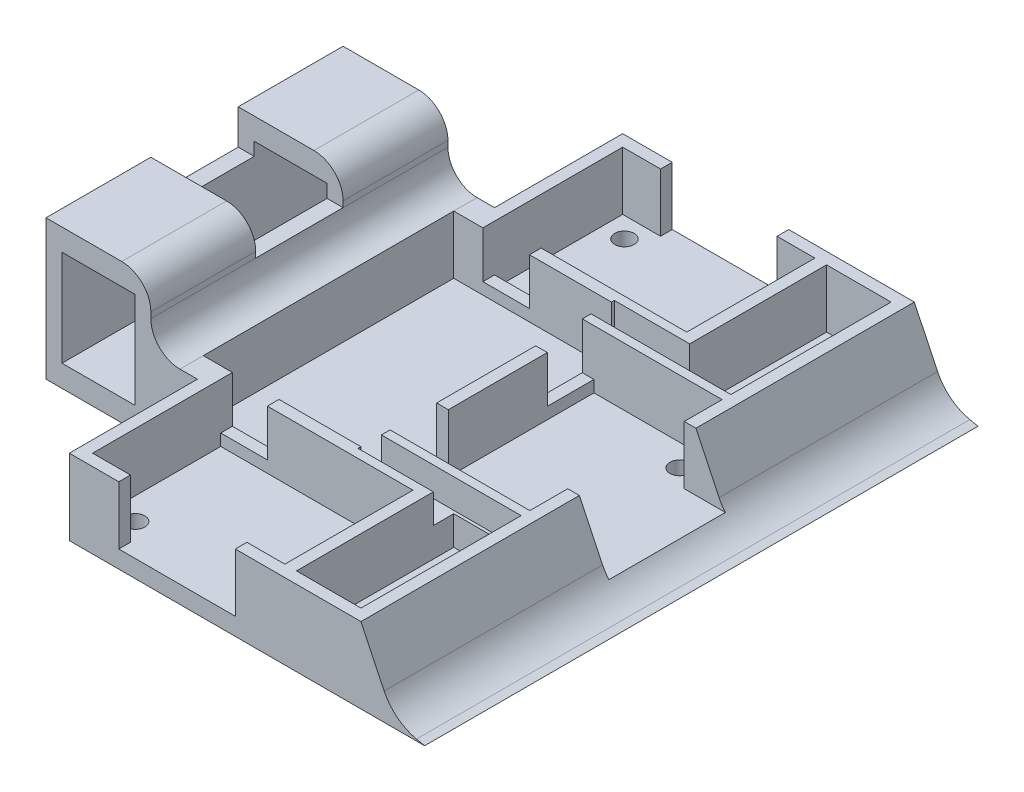
SolidWorks part; units mm, degrees
ref_plane "Front Plane" through (0, 0, 0) normal (0, 0, 1) x (1, 0, 0)
ref_plane "Top Plane" through (0, 0, 0) normal (0, 1, 0) x (1, 0, 0)
ref_plane "Right Plane" through (0, 0, 0) normal (1, 0, 0) x (0, 0, -1)
sketch "Sketch1" plane through (0, 0, 0) normal (0, 1, 0) x (1, 0, 0)
  line L1 (-47.5, -47.5) -> (47.5, -47.5)
  line L2 (-47.5, -47.5) -> (-47.5, 47.5)
  line L3 (-47.5, 47.5) -> (47.5, 47.5)
  line L4 (47.5, -47.5) -> (47.5, 47.5)
  line L5 (-47.5, -47.5) -> (47.5, 47.5) construction
  line L6 (-47.5, 47.5) -> (47.5, -47.5) construction
  point P0 (0, 0)
  dimension "D1" = 95
  dimension "D2" = 95
extrude "Boss-Extrude2" add sketch "Sketch1" along normal blind 13
sketch "Sketch2" plane through (-47.5, 0, 0) normal (-1, 0, 0) x (0, 0, 1)
  line L0 (-47.5, 13) -> (47.5, 13) construction
  line L1 (47.5, 0) -> (25.5, 0)
  line L2 (47.5, 0) -> (47.5, 13)
  line L3 (47.5, 13) -> (25.5, 13)
  line L4 (25.5, 0) -> (25.5, 13)
  dimension "D1" = 22
extrude "Cut-Extrude1" cut sketch "Sketch2" against normal blind 34
sketch "Sketch3" plane through (-47.5, 0, 0) normal (-1, 0, 0) x (0, 0, 1)
  line L0 (-47.5, 0) -> (25.5, 0) construction
  line L1 (-47.5, 13) -> (-25.5, 13)
  line L2 (-47.5, 13) -> (-47.5, 0)
  line L3 (-47.5, 0) -> (-25.5, 0)
  line L4 (-25.5, 13) -> (-25.5, 0)
  dimension "D1" = 22
extrude "Cut-Extrude2" cut sketch "Sketch3" against normal blind 34
sketch "Sketch5" plane through (0, 13, 0) normal (0, 1, 0) x (1, 0, 0)
  line L0 (-13.5, -25.5) -> (-47.5, -25.5) construction
  line L1 (-47.5, 25.5) -> (-21.5, 25.5)
  line L2 (-47.5, 25.5) -> (-47.5, -25.5)
  line L3 (-47.5, -25.5) -> (-21.5, -25.5)
  line L4 (-21.5, 25.5) -> (-21.5, -25.5)
  dimension "D1" = 26
extrude "Boss-Extrude3" add sketch "Sketch5" along normal blind 20
sketch "Sketch6" plane through (0, 0, 25.5) normal (0, 0, 1) x (1, 0, 0)
  line L0 (-13.5, 0) -> (-47.5, 0) construction
  line L1 (-36.5, 20) -> (-24.5, 20)
  line L2 (-36.5, 20) -> (-36.5, 4)
  line L3 (-36.5, 4) -> (-24.5, 4)
  line L4 (-24.5, 20) -> (-24.5, 4)
  line L5 (-47.5, 33) -> (-47.5, 0) construction
  line L6 (-13.5, 0) -> (-13.5, 13) construction
  dimension "D1" = 12
  dimension "D2" = 16
  dimension "D3" = 4
  dimension "D4" = 11
  dimension "D5" = 11
extrude "Cut-Extrude4" cut sketch "Sketch6" against normal blind 200
sketch "Sketch7" plane through (0, 0, 25.5) normal (0, 0, 1) x (1, 0, 0)
  line L0 (-21.5, 33) -> (-21.5, 13) construction
  line L1 (-47.5, 33) -> (-21.5, 33)
  line L2 (-47.5, 33) -> (-47.5, 24)
  line L3 (-47.5, 24) -> (-21.5, 24)
  line L4 (-21.5, 33) -> (-21.5, 24)
  dimension "D1" = 4
extrude "Cut-Extrude5" cut sketch "Sketch7" against normal blind 200
fillet "Fillet2" radius 5 2 edges at (-21.5, 24, 0)
sketch "Sketch8" plane through (0, 0, 25.5) normal (0, 0, 1) x (1, 0, 0)
  line L0 (-13.5, 0) -> (-47.5, 0) construction
  line L1 (-47.5, 24) -> (-39.5, 24)
  line L2 (-47.5, 24) -> (-47.5, 0)
  line L3 (-47.5, 0) -> (-39.5, 0)
  line L4 (-39.5, 24) -> (-39.5, 0)
  dimension "D1" = 3
extrude "Cut-Extrude6" cut sketch "Sketch8" against normal blind 200
sketch "Sketch9" plane through (0, 13, 0) normal (0, 1, 0) x (1, 0, 0)
  line L0 (-13.5, -47.5) -> (47.5, -47.5) construction
  line L1 (-11.5, -23.5) -> (21.5, -23.5)
  line L2 (-11.5, -23.5) -> (-11.5, -45.5)
  line L3 (-11.5, -45.5) -> (21.5, -45.5)
  line L4 (21.5, -23.5) -> (21.5, -45.5)
  dimension "D1" = 33
  dimension "D2" = 22
  dimension "D3" = 2
  dimension "D4" = 2
extrude "Cut-Extrude7" cut sketch "Sketch9" against normal blind 10
sketch "Sketch10" plane through (0, 0, 47.5) normal (0, 0, 1) x (1, 0, 0)
  line L0 (-13.5, 0) -> (47.5, 0) construction
  line L1 (-5, 13) -> (15, 13)
  line L2 (-5, 13) -> (-5, 3)
  line L3 (-5, 3) -> (15, 3)
  line L4 (15, 13) -> (15, 3)
  dimension "D1" = 20
  dimension "D2" = 10
  dimension "D3" = 3
  dimension "D4" = 6.5
extrude "Cut-Extrude10" cut sketch "Sketch10" against normal blind 10
sketch "Sketch13" plane through (0, 13, 0) normal (0, 1, 0) x (1, 0, 0)
  line L0 (47.5, 47.5) -> (-13.5, 47.5) construction
  line L1 (-11.5, 45.5) -> (21.5, 45.5)
  line L2 (-11.5, 45.5) -> (-11.5, 23.5)
  line L3 (-11.5, 23.5) -> (21.5, 23.5)
  line L4 (21.5, 45.5) -> (21.5, 23.5)
  line L5 (-13.5, 25.5) -> (-13.5, 47.5) construction
  dimension "D1" = 22
  dimension "D2" = 33
  dimension "D3" = 2
  dimension "D4" = 2
extrude "Cut-Extrude11" cut sketch "Sketch13" against normal blind 10
sketch "Sketch14" plane through (0, 0, -47.5) normal (0, 0, -1) x (-1, 0, 0)
  line L0 (-47.5, 13) -> (13.5, 13) construction
  line L1 (-15, 13) -> (5, 13)
  line L2 (-15, 13) -> (-15, 3)
  line L3 (-15, 3) -> (5, 3)
  line L4 (5, 13) -> (5, 3)
  dimension "D1" = 20
  dimension "D2" = 10
  dimension "D3" = 8.5
extrude "Cut-Extrude12" cut sketch "Sketch14" against normal blind 10
sketch "Sketch18" plane through (47.5, 0, 0) normal (1, 0, 0) x (0, 0, -1)
  line L0 (-47.5, 13) -> (47.5, 13) construction
  line L1 (10, 13) -> (-10, 13)
  line L2 (10, 13) -> (10, 3)
  line L3 (10, 3) -> (-10, 3)
  line L4 (-10, 13) -> (-10, 3)
  dimension "D1" = 10
  dimension "D2" = 20
  dimension "D3" = 13.5
  dimension "D4" = 13.5
extrude "Cut-Extrude16" cut sketch "Sketch18" against normal blind 50
sketch "Sketch19" plane through (0, 0, 47.5) normal (0, 0, 1) x (1, 0, 0)
  line L0 (47.5, 0) -> (42.2527, 1.1202)
  line L1 (42.2527, 1.1202) -> (36.5702, 13)
  line L2 (15, 13) -> (47.5, 13) construction
  line L4 (36.5702, 13) -> (47.5, 13)
  line L7 (47.5, 13) -> (47.5, 0)
extrude "Cut-Extrude17" cut sketch "Sketch19" against normal blind 100000
sketch "Sketch20" plane through (0, 13, 0) normal (0, 1, 0) x (1, 0, 0)
  line L1 (34.5702, -16.5) -> (12.5702, -16.5)
  line L2 (34.5702, -16.5) -> (34.5702, 16.5)
  line L3 (34.5702, 16.5) -> (12.5702, 16.5)
  line L4 (12.5702, -16.5) -> (12.5702, 16.5)
  line L5 (36.5702, -10) -> (36.5702, -47.5) construction
  dimension "D1" = 22
  dimension "D2" = 33
  dimension "D3" = 6.5
  dimension "D4" = 2
extrude "Cut-Extrude18" cut sketch "Sketch20" against normal blind 10
sketch "Sketch21" plane through (0, 13, 0) normal (0, 1, 0) x (1, 0, 0)
  line L0 (-16.5, 25.5) -> (-16.5, -25.5) construction
  line L1 (-16.5, -21.5) -> (10.5702, -21.5)
  line L2 (-16.5, -21.5) -> (-16.5, 21.5)
  line L3 (-16.5, 21.5) -> (10.5702, 21.5)
  line L4 (10.5702, -21.5) -> (10.5702, 21.5)
  dimension "D1" = 2
  dimension "D2" = 2
  dimension "D3" = 2
extrude "Cut-Extrude19" cut sketch "Sketch21" against normal blind 10
sketch "Sketch22" plane through (0, 3, 0) normal (0, 1, 0) x (1, 0, 0)
  line L1 (12.5702, -10) -> (10.5702, -10)
  line L2 (12.5702, -10) -> (12.5702, 10)
  line L3 (12.5702, 10) -> (10.5702, 10)
  line L4 (10.5702, -10) -> (10.5702, 10)
extrude "Boss-Extrude4" add sketch "Sketch22" along normal blind 10
sketch "Sketch23" plane through (0, 0, 25.5) normal (0, 0, 1) x (1, 0, 0)
  line L0 (-24.5, 20) -> (-36.5, 20) construction
  line L1 (-36.75, 20.25) -> (-24.25, 20.25)
  line L2 (-36.75, 20.25) -> (-36.75, 3.75)
  line L3 (-36.75, 3.75) -> (-24.25, 3.75)
  line L4 (-24.25, 20.25) -> (-24.25, 3.75)
  line L5 (-24.5, 4) -> (-24.5, 20) construction
  dimension "D1" = 12.5
  dimension "D2" = 16.5
  dimension "D3" = 0.25
  dimension "D4" = 0.25
extrude "Cut-Extrude20" cut sketch "Sketch23" against normal blind 200
sketch "Sketch24" plane through (0, 13, 0) normal (0, 1, 0) x (1, 0, 0)
  line L0 (-16.5, -21.5) -> (10.5702, -21.5) construction
  line L1 (-11.5, -23.5) -> (-3.5, -23.5)
  line L2 (-11.5, -23.5) -> (-11.5, -21.5)
  line L3 (-11.5, -21.5) -> (-3.5, -21.5)
  line L4 (-3.5, -23.5) -> (-3.5, -21.5)
  dimension "D1" = 8
extrude "Cut-Extrude21" cut sketch "Sketch24" against normal blind 8
sketch "Sketch25" plane through (0, 13, 0) normal (0, 1, 0) x (1, 0, 0)
  line L0 (10.5702, 21.5) -> (-16.5, 21.5) construction
  line L1 (-11.5, 23.5) -> (-3.5, 23.5)
  line L2 (-11.5, 23.5) -> (-11.5, 21.5)
  line L3 (-11.5, 21.5) -> (-3.5, 21.5)
  line L4 (-3.5, 23.5) -> (-3.5, 21.5)
  dimension "D1" = 8
extrude "Cut-Extrude22" cut sketch "Sketch25" against normal blind 8
sketch "Sketch26" plane through (0, 13, 0) normal (0, 1, 0) x (1, 0, 0)
  line L0 (10.5702, -21.5) -> (10.5702, 21.5) construction
  line L1 (12.5702, -16.5) -> (10.5702, -16.5)
  line L2 (12.5702, -16.5) -> (12.5702, -8.5)
  line L3 (12.5702, -8.5) -> (10.5702, -8.5)
  line L4 (10.5702, -16.5) -> (10.5702, -8.5)
  dimension "D1" = 8
extrude "Cut-Extrude24" cut sketch "Sketch26" against normal blind 8
sketch "Sketch27" plane through (0, 13, 0) normal (0, 1, 0) x (1, 0, 0)
  line L0 (10.5702, -8.5) -> (10.5702, 21.5) construction
  line L1 (12.5702, 16.5) -> (10.5702, 16.5)
  line L2 (12.5702, 16.5) -> (12.5702, 8.5)
  line L3 (12.5702, 8.5) -> (10.5702, 8.5)
  line L4 (10.5702, 16.5) -> (10.5702, 8.5)
  dimension "D1" = 8
extrude "Cut-Extrude25" cut sketch "Sketch27" against normal blind 8
sketch "Sketch28" plane through (0, 13, 0) normal (0, 1, 0) x (1, 0, 0)
  line L0 (36.5702, -10) -> (36.5702, -47.5) construction
  line L1 (23.5, -18.5) -> (34.5702, -18.5)
  line L2 (23.5, -18.5) -> (23.5, -45.5)
  line L3 (23.5, -45.5) -> (34.5702, -45.5)
  line L4 (34.5702, -18.5) -> (34.5702, -45.5)
  line L5 (21.5, -45.5) -> (21.5, -23.5) construction
  line L6 (15, -47.5) -> (36.5702, -47.5) construction
  dimension "D1" = 2
  dimension "D2" = 2
  dimension "D3" = 2
  dimension "D4" = 2
extrude "Cut-Extrude26" cut sketch "Sketch28" against normal blind 10
sketch "Sketch29" plane through (0, 13, 0) normal (0, 1, 0) x (1, 0, 0)
  line L0 (36.5702, 47.5) -> (36.5702, 10) construction
  line L1 (23.5, 45.5) -> (34.5702, 45.5)
  line L2 (23.5, 45.5) -> (23.5, 18.5)
  line L3 (23.5, 18.5) -> (34.5702, 18.5)
  line L4 (34.5702, 45.5) -> (34.5702, 18.5)
  line L5 (21.5, 23.5) -> (21.5, 45.5) construction
  line L6 (36.5702, 47.5) -> (15, 47.5) construction
  dimension "D1" = 2
  dimension "D2" = 2
  dimension "D3" = 2
  dimension "D4" = 2
extrude "Cut-Extrude27" cut sketch "Sketch29" against normal blind 10
sketch "Sketch30" plane through (0, 13, 0) normal (0, 1, 0) x (1, 0, 0)
  line L1 (10.5702, -22) -> (34.5702, -22)
  line L2 (10.5702, -22) -> (10.5702, -18)
  line L3 (10.5702, -18) -> (34.5702, -18)
  line L4 (34.5702, -22) -> (34.5702, -18)
  line L5 (21.5, -23.5) -> (-3.5, -23.5) construction
  line L6 (10.5702, -16.5) -> (34.5702, -16.5) construction
  line L7 (10.5702, -21.5) -> (10.5702, 21.5) construction
  dimension "D1" = 0
  dimension "D2" = 1.5
  dimension "D3" = 1.5
  dimension "D4" = 0
extrude "Cut-Extrude29" cut sketch "Sketch30" against normal blind 5
sketch "Sketch31" plane through (0, 13, 0) normal (0, 1, 0) x (1, 0, 0)
  line L0 (-3.5, 23.5) -> (21.5, 23.5) construction
  line L1 (10.5702, 22) -> (34.5702, 22)
  line L2 (10.5702, 22) -> (10.5702, 18)
  line L3 (10.5702, 18) -> (34.5702, 18)
  line L4 (34.5702, 22) -> (34.5702, 18)
  line L5 (34.5702, 16.5) -> (10.5702, 16.5) construction
  line L6 (10.5702, -21.5) -> (10.5702, 21.5) construction
  dimension "D1" = 1.5
  dimension "D2" = 1.5
  dimension "D3" = 0
  dimension "D4" = 0
extrude "Cut-Extrude30" cut sketch "Sketch31" against normal blind 5
sketch "Sketch32" plane through (0, 3, 0) normal (0, 1, 0) x (1, 0, 0)
  line L0 (34.5702, -45.5) -> (34.5702, -18.5) construction
  line L1 (26.5352, -36.5) -> (31.5352, -36.5)
  line L2 (26.5352, -36.5) -> (26.5352, -41.5)
  line L3 (26.5352, -41.5) -> (31.5352, -41.5)
  line L4 (31.5352, -36.5) -> (31.5352, -41.5)
  line L5 (23.5, -18.5) -> (23.5, -45.5) construction
  line L6 (23.5, -45.5) -> (34.5702, -45.5) construction
  dimension "D1" = 5
  dimension "D2" = 5
  dimension "D3" = 3.035
  dimension "D4" = 3.0352
  dimension "D5" = 4
extrude "Cut-Extrude32" cut sketch "Sketch32" against normal blind 5
sketch "Sketch40" plane through (0, 3, 0) normal (0, 1, 0) x (1, 0, 0)
  line L0 (34.5702, 45.5) -> (23.5, 45.5) construction
  line L1 (26.535, 41.5) -> (31.535, 41.5)
  line L2 (26.535, 41.5) -> (26.535, 31.5)
  line L3 (26.535, 31.5) -> (31.535, 31.5)
  line L4 (31.535, 41.5) -> (31.535, 31.5)
  line L5 (23.5, 45.5) -> (23.5, 18.5) construction
  dimension "D1" = 10
  dimension "D2" = 5
  dimension "D3" = 4
  dimension "D4" = 3.035
extrude "Cut-Extrude39" cut sketch "Sketch40" against normal blind 5
sketch "Sketch41" plane through (0, 3, 0) normal (0, 1, 0) x (1, 0, 0)
  line L0 (26.535, 31.5) -> (31.535, 31.5) construction
  circle A0 centre (29.035, 28.5) radius 1.2
  point P2 (29.035, 31.5)
  dimension "D1" = 2.5
  dimension "D2" = 3
extrude "Cut-Extrude40" cut sketch "Sketch41" against normal blind 5
sketch "Sketch42" plane through (0, 3, 0) normal (0, 1, 0) x (1, 0, 0)
  line L1 (26.5352, -31.5) -> (31.5352, -31.5)
  line L2 (26.5352, -31.5) -> (26.5352, -36.5)
  line L3 (26.5352, -36.5) -> (31.5352, -36.5)
  line L4 (31.5352, -31.5) -> (31.5352, -36.5)
  dimension "D1" = 5
extrude "Cut-Extrude41" cut sketch "Sketch42" against normal blind 5
sketch "Sketch43" plane through (0, 3, 0) normal (0, 1, 0) x (1, 0, 0)
  line L0 (31.5352, -31.5) -> (26.5352, -31.5) construction
  circle A0 centre (29.0352, -28.5) radius 1.2
  dimension "D1" = 3
  dimension "D2" = 2.5
extrude "Cut-Extrude42" cut sketch "Sketch43" against normal blind 5
sketch "Sketch44" plane through (0, 3, 0) normal (0, 1, 0) x (1, 0, 0)
  line L0 (-5, 45.5) -> (-11.5, 45.5) construction
  line L1 (-11.5, 45.5) -> (-11.5, 23.5) construction
  line L3 (21.5, 23.5) -> (21.5, 45.5) construction
  circle A0 centre (-7.7, 42) radius 1.666
  circle A1 centre (17.7, 42) radius 1.666
  dimension "D1" = 3.5
  dimension "D2" = 25.4
  dimension "D3" = 3.8
  dimension "D4" = 3.8
extrude "Cut-Extrude43" cut sketch "Sketch44" against normal blind 5
sketch "Sketch45" plane through (0, 3, 0) normal (0, 1, 0) x (1, 0, 0)
  line L0 (-11.5, -45.5) -> (-5, -45.5) construction
  line L1 (-11.5, -23.5) -> (-11.5, -45.5) construction
  line L2 (21.5, -45.5) -> (21.5, -23.5) construction
  circle A0 centre (-7.7, -42) radius 1.666
  circle A1 centre (17.7, -42) radius 1.666
  point P2 (-8.25, -45.5)
  dimension "D1" = 3.5
  dimension "D3" = 3.8
  dimension "D2" = 3.8
extrude "Cut-Extrude44" cut sketch "Sketch45" against normal blind 5
sketch "Sketch46" plane through (0, 3, 0) normal (0, 1, 0) x (1, 0, 0)
  line L0 (12.5702, -16.5) -> (34.5702, -16.5) construction
  line L1 (34.5702, -16.5) -> (34.5702, -10) construction
  line L2 (34.5702, 16.5) -> (12.5702, 16.5) construction
  circle A0 centre (31.0702, -12.7) radius 1.666
  circle A1 centre (31.0702, 12.7) radius 1.666
  dimension "D1" = 3.8
  dimension "D3" = 3.8
  dimension "D2" = 3.5
extrude "Cut-Extrude45" cut sketch "Sketch46" against normal blind 5
fillet "Fillet6" radius 8 1 edges at (42.2527, 1.1202, 0)
sketch "Sketch47" plane through (-39.5, 0, 0) normal (-1, 0, 0) x (0, 0, 1)
  line L0 (-25.5, 24) -> (25.5, 24) construction
  line L1 (-7.5, 24) -> (7.5, 24)
  line L2 (-7.5, 24) -> (-7.5, 18)
  line L3 (-7.5, 18) -> (7.5, 18)
  line L4 (7.5, 24) -> (7.5, 18)
  line L5 (25.5, 0) -> (25.5, 24) construction
  line L6 (-25.5, 0) -> (-25.5, 13) construction
  dimension "D1" = 15
  dimension "D2" = 6
  dimension "D3" = 18
  dimension "D4" = 18
extrude "Cut-Extrude46" cut sketch "Sketch47" against normal blind 100
